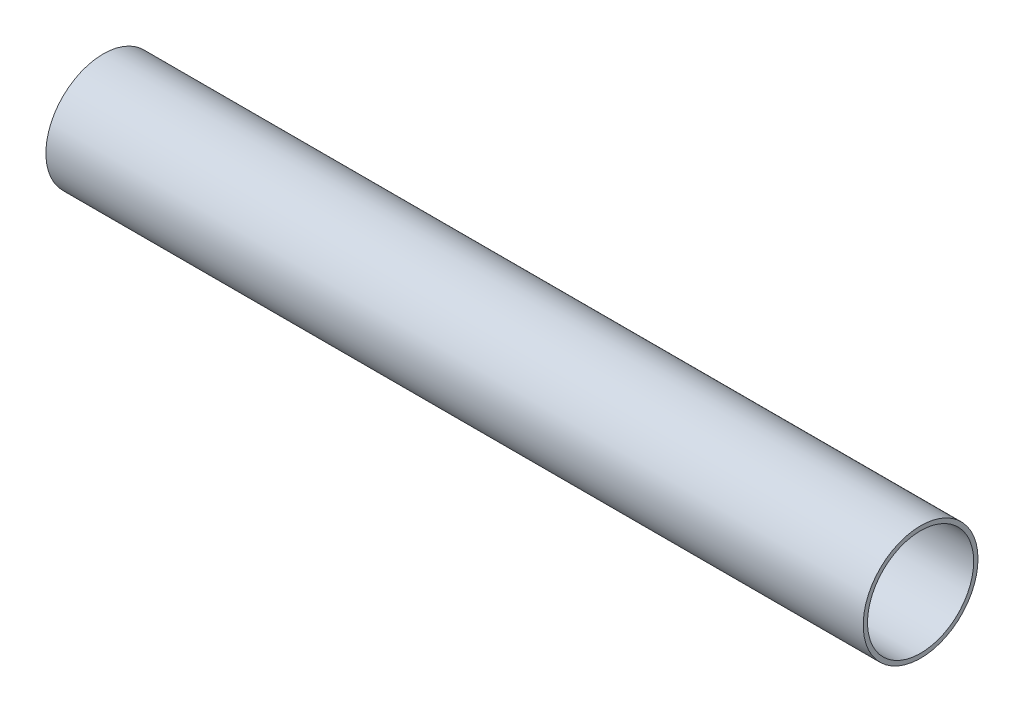
SolidWorks part; units mm, degrees
material "Silicon Rubber"
ref_plane "Front Plane" through (0, 0, 0) normal (0, 0, 1) x (1, 0, 0)
ref_plane "Top Plane" through (0, 0, 0) normal (0, 1, 0) x (1, 0, 0)
ref_plane "Right Plane" through (0, 0, 0) normal (1, 0, 0) x (0, 0, -1)
sketch "Sketch1" plane through (0, 0, 0) normal (1, 0, 0) x (0, 0, -1)
  circle A0 centre (0, 0) radius 15.875
  circle A1 centre (0, 0) radius 17.1714
  dimension "D1" = 31.75
  dimension "D2" = 34.3429
extrude "Boss-Extrude1" add sketch "Sketch1" along normal mid plane 244.4432
equation "\"D2@Sketch1\"=sqr((1.25)^2+(1.125)^2-1)"
